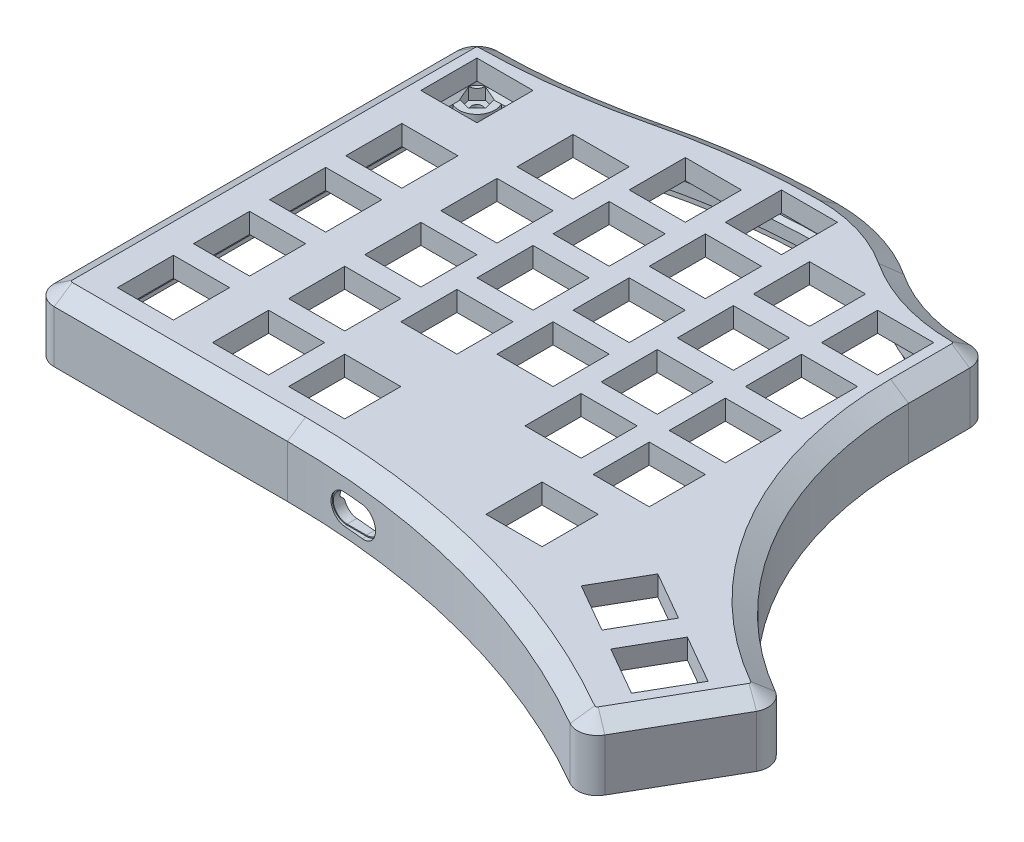
SolidWorks part; units mm, degrees
ref_plane "Front Plane" through (0, 0, 0) normal (0, 0, 1) x (1, 0, 0)
ref_plane "Top Plane" through (0, 0, 0) normal (0, 1, 0) x (1, 0, 0)
ref_plane "Right Plane" through (0, 0, 0) normal (1, 0, 0) x (0, 0, -1)
sketch "Main" plane through (0, 0, 0) normal (0, 1, 0) x (1, 0, 0)
  line L0 (6.4754, 3.5) -> (12.8, 6.5) construction
  line L1 (0, 0) -> (18, 0) construction
  line L2 (0, 0) -> (0, 18) construction
  line L3 (0, 18) -> (18, 18) construction
  line L4 (18, 0) -> (18, 18) construction
  line L5 (2, 16) -> (16, 16)
  line L6 (2, 16) -> (2, 2)
  line L7 (2, 2) -> (16, 2)
  line L8 (16, 16) -> (16, 2)
  line L18 (9, 9) -> (6.4754, 3.5) construction
  line L20 (9, 9) -> (12.8, 6.5) construction
  line L22 (25.4754, 12.5) -> (31.8, 15.5) construction
  line L23 (19, 9) -> (37, 9) construction
  line L24 (19, 9) -> (19, 27) construction
  line L25 (19, 27) -> (37, 27) construction
  line L26 (37, 9) -> (37, 27) construction
  line L27 (21, 25) -> (35, 25)
  line L28 (21, 25) -> (21, 11)
  line L29 (21, 11) -> (35, 11)
  line L30 (35, 25) -> (35, 11)
  line L31 (28, 18) -> (25.4754, 12.5) construction
  line L32 (28, 18) -> (31.8, 15.5) construction
  line L33 (44.4754, 17.5) -> (50.8, 20.5) construction
  line L34 (38, 14) -> (56, 14) construction
  line L35 (38, 14) -> (38, 32) construction
  line L36 (38, 32) -> (56, 32) construction
  line L37 (56, 14) -> (56, 32) construction
  line L38 (40, 30) -> (54, 30)
  line L39 (40, 30) -> (40, 16)
  line L40 (40, 16) -> (54, 16)
  line L41 (54, 30) -> (54, 16)
  line L42 (47, 23) -> (44.4754, 17.5) construction
  line L43 (47, 23) -> (50.8, 20.5) construction
  line L44 (63.4754, 5.5) -> (69.8, 8.5) construction
  line L45 (57, 2) -> (75, 2) construction
  line L46 (57, 2) -> (57, 20) construction
  line L47 (57, 20) -> (75, 20) construction
  line L48 (75, 2) -> (75, 20) construction
  line L49 (59, 18) -> (73, 18)
  line L50 (59, 18) -> (59, 4)
  line L51 (59, 4) -> (73, 4)
  line L52 (73, 18) -> (73, 4)
  line L53 (66, 11) -> (63.4754, 5.5) construction
  line L54 (66, 11) -> (69.8, 8.5) construction
  line L55 (82.4754, 3.5) -> (88.8, 6.5) construction
  line L56 (76, 0) -> (94, 0) construction
  line L57 (76, 0) -> (76, 18) construction
  line L58 (76, 18) -> (94, 18) construction
  line L59 (94, 0) -> (94, 18) construction
  line L60 (78, 16) -> (92, 16)
  line L61 (78, 16) -> (78, 2)
  line L62 (78, 2) -> (92, 2)
  line L63 (92, 16) -> (92, 2)
  line L64 (85, 9) -> (82.4754, 3.5) construction
  line L65 (85, 9) -> (88.8, 6.5) construction
  line L88 (2, -3) -> (16, -3)
  line L89 (2, -3) -> (2, -17)
  line L90 (2, -17) -> (16, -17)
  line L91 (16, -3) -> (16, -17)
  line L92 (21, 6) -> (35, 6)
  line L93 (21, 6) -> (21, -8)
  line L94 (21, -8) -> (35, -8)
  line L95 (35, 6) -> (35, -8)
  line L96 (40, 11) -> (54, 11)
  line L97 (40, 11) -> (40, -3)
  line L98 (40, -3) -> (54, -3)
  line L99 (54, 11) -> (54, -3)
  line L100 (59, -1) -> (73, -1)
  line L101 (59, -1) -> (59, -15)
  line L102 (59, -15) -> (73, -15)
  line L103 (73, -1) -> (73, -15)
  line L104 (78, -3) -> (92, -3)
  line L105 (78, -3) -> (78, -17)
  line L106 (78, -17) -> (92, -17)
  line L107 (92, -3) -> (92, -17)
  line L116 (6.4754, -15.5) -> (12.8, -12.5) construction
  line L117 (0, -19) -> (18, -19) construction
  line L118 (0, -19) -> (0, -1) construction
  line L119 (0, -1) -> (18, -1) construction
  line L120 (18, -19) -> (18, -1) construction
  line L121 (9, -10) -> (6.4754, -15.5) construction
  line L122 (9, -10) -> (12.8, -12.5) construction
  line L123 (25.4754, -6.5) -> (31.8, -3.5) construction
  line L124 (19, -10) -> (37, -10) construction
  line L125 (19, -10) -> (19, 8) construction
  line L126 (19, 8) -> (37, 8) construction
  line L127 (37, -10) -> (37, 8) construction
  line L128 (28, -1) -> (25.4754, -6.5) construction
  line L129 (28, -1) -> (31.8, -3.5) construction
  line L130 (44.4754, -1.5) -> (50.8, 1.5) construction
  line L131 (38, -5) -> (56, -5) construction
  line L132 (38, -5) -> (38, 13) construction
  line L133 (38, 13) -> (56, 13) construction
  line L134 (56, -5) -> (56, 13) construction
  line L135 (47, 4) -> (44.4754, -1.5) construction
  line L136 (47, 4) -> (50.8, 1.5) construction
  line L137 (63.4754, -13.5) -> (69.8, -10.5) construction
  line L138 (57, -17) -> (75, -17) construction
  line L139 (57, -17) -> (57, 1) construction
  line L140 (57, 1) -> (75, 1) construction
  line L141 (75, -17) -> (75, 1) construction
  line L142 (66, -8) -> (63.4754, -13.5) construction
  line L143 (66, -8) -> (69.8, -10.5) construction
  line L144 (82.4754, -15.5) -> (88.8, -12.5) construction
  line L145 (76, -19) -> (94, -19) construction
  line L146 (76, -19) -> (76, -1) construction
  line L147 (76, -1) -> (94, -1) construction
  line L148 (94, -19) -> (94, -1) construction
  line L149 (85, -10) -> (82.4754, -15.5) construction
  line L150 (85, -10) -> (88.8, -12.5) construction
  line L165 (2, -22) -> (16, -22)
  line L166 (2, -22) -> (2, -36)
  line L167 (2, -36) -> (16, -36)
  line L168 (16, -22) -> (16, -36)
  line L169 (21, -13) -> (35, -13)
  line L170 (21, -13) -> (21, -27)
  line L171 (21, -27) -> (35, -27)
  line L172 (35, -13) -> (35, -27)
  line L173 (40, -8) -> (54, -8)
  line L174 (40, -8) -> (40, -22)
  line L175 (40, -22) -> (54, -22)
  line L176 (54, -8) -> (54, -22)
  line L177 (59, -20) -> (73, -20)
  line L178 (59, -20) -> (59, -34)
  line L179 (59, -34) -> (73, -34)
  line L180 (73, -20) -> (73, -34)
  line L181 (78, -22) -> (92, -22)
  line L182 (78, -22) -> (78, -36)
  line L183 (78, -36) -> (92, -36)
  line L184 (92, -22) -> (92, -36)
  line L193 (6.4754, -34.5) -> (12.8, -31.5) construction
  line L194 (0, -38) -> (18, -38) construction
  line L195 (0, -38) -> (0, -20) construction
  line L196 (0, -20) -> (18, -20) construction
  line L197 (18, -38) -> (18, -20) construction
  line L198 (9, -29) -> (6.4754, -34.5) construction
  line L199 (9, -29) -> (12.8, -31.5) construction
  line L200 (25.4754, -25.5) -> (31.8, -22.5) construction
  line L201 (19, -29) -> (37, -29) construction
  line L202 (19, -29) -> (19, -11) construction
  line L203 (19, -11) -> (37, -11) construction
  line L204 (37, -29) -> (37, -11) construction
  line L205 (28, -20) -> (25.4754, -25.5) construction
  line L206 (28, -20) -> (31.8, -22.5) construction
  line L207 (44.4754, -20.5) -> (50.8, -17.5) construction
  line L208 (38, -24) -> (56, -24) construction
  line L209 (38, -24) -> (38, -6) construction
  line L210 (38, -6) -> (56, -6) construction
  line L211 (56, -24) -> (56, -6) construction
  line L212 (47, -15) -> (44.4754, -20.5) construction
  line L213 (47, -15) -> (50.8, -17.5) construction
  line L214 (63.4754, -32.5) -> (69.8, -29.5) construction
  line L215 (57, -36) -> (75, -36) construction
  line L216 (57, -36) -> (57, -18) construction
  line L217 (57, -18) -> (75, -18) construction
  line L218 (75, -36) -> (75, -18) construction
  line L219 (66, -27) -> (63.4754, -32.5) construction
  line L220 (66, -27) -> (69.8, -29.5) construction
  line L221 (82.4754, -34.5) -> (88.8, -31.5) construction
  line L222 (76, -38) -> (94, -38) construction
  line L223 (76, -38) -> (76, -20) construction
  line L224 (76, -20) -> (94, -20) construction
  line L225 (94, -38) -> (94, -20) construction
  line L226 (85, -29) -> (82.4754, -34.5) construction
  line L227 (85, -29) -> (88.8, -31.5) construction
  line L242 (2, -41) -> (16, -41)
  line L243 (2, -41) -> (2, -55)
  line L244 (2, -55) -> (16, -55)
  line L245 (16, -41) -> (16, -55)
  line L246 (21, -32) -> (35, -32)
  line L247 (21, -32) -> (21, -46)
  line L248 (21, -46) -> (35, -46)
  line L249 (35, -32) -> (35, -46)
  line L250 (40, -27) -> (54, -27)
  line L251 (40, -27) -> (40, -41)
  line L252 (40, -41) -> (54, -41)
  line L253 (54, -27) -> (54, -41)
  line L254 (59, -39) -> (73, -39)
  line L255 (59, -39) -> (59, -53)
  line L256 (59, -53) -> (73, -53)
  line L257 (73, -39) -> (73, -53)
  line L258 (78, -41) -> (92, -41)
  line L259 (78, -41) -> (78, -55)
  line L260 (78, -55) -> (92, -55)
  line L261 (92, -41) -> (92, -55)
  line L270 (6.4754, -53.5) -> (12.8, -50.5) construction
  line L271 (0, -57) -> (18, -57) construction
  line L272 (0, -57) -> (0, -39) construction
  line L273 (0, -39) -> (18, -39) construction
  line L274 (18, -57) -> (18, -39) construction
  line L275 (9, -48) -> (6.4754, -53.5) construction
  line L276 (9, -48) -> (12.8, -50.5) construction
  line L277 (25.4754, -44.5) -> (31.8, -41.5) construction
  line L278 (19, -48) -> (37, -48) construction
  line L279 (19, -48) -> (19, -30) construction
  line L280 (19, -30) -> (37, -30) construction
  line L281 (37, -48) -> (37, -30) construction
  line L282 (28, -39) -> (25.4754, -44.5) construction
  line L283 (28, -39) -> (31.8, -41.5) construction
  line L284 (44.4754, -39.5) -> (50.8, -36.5) construction
  line L285 (38, -43) -> (56, -43) construction
  line L286 (38, -43) -> (38, -25) construction
  line L287 (38, -25) -> (56, -25) construction
  line L288 (56, -43) -> (56, -25) construction
  line L289 (47, -34) -> (44.4754, -39.5) construction
  line L290 (47, -34) -> (50.8, -36.5) construction
  line L291 (63.4754, -51.5) -> (69.8, -48.5) construction
  line L292 (57, -55) -> (75, -55) construction
  line L293 (57, -55) -> (57, -37) construction
  line L294 (57, -37) -> (75, -37) construction
  line L295 (75, -55) -> (75, -37) construction
  line L296 (66, -46) -> (63.4754, -51.5) construction
  line L297 (66, -46) -> (69.8, -48.5) construction
  line L298 (82.4754, -53.5) -> (88.8, -50.5) construction
  line L299 (76, -57) -> (94, -57) construction
  line L300 (76, -57) -> (76, -39) construction
  line L301 (76, -39) -> (94, -39) construction
  line L302 (94, -57) -> (94, -39) construction
  line L303 (85, -48) -> (82.4754, -53.5) construction
  line L304 (85, -48) -> (88.8, -50.5) construction
  line L312 (6.4754, -72.5) -> (12.8, -69.5) construction
  line L313 (0, -76) -> (18, -76) construction
  line L314 (0, -76) -> (0, -58) construction
  line L315 (0, -58) -> (18, -58) construction
  line L316 (18, -76) -> (18, -58) construction
  line L317 (2, -60) -> (16, -60)
  line L318 (2, -60) -> (2, -74)
  line L323 (21, -60) -> (35, -60)
  line L324 (21, -60) -> (21, -74)
  line L325 (21, -74) -> (35, -74)
  line L326 (35, -60) -> (35, -74)
  line L327 (25.4754, -72.5) -> (31.8, -69.5) construction
  line L328 (19, -76) -> (37, -76) construction
  line L329 (19, -76) -> (19, -58) construction
  line L330 (-22.0246, 8) -> (-15.7, 11) construction
  line L331 (-28.5, 4.5) -> (-10.5, 4.5) construction
  line L332 (-28.5, 4.5) -> (-28.5, 22.5) construction
  line L333 (-28.5, 22.5) -> (-10.5, 22.5) construction
  line L334 (-10.5, 4.5) -> (-10.5, 22.5) construction
  line L335 (-26.5, 20.5) -> (-12.5, 20.5)
  line L336 (-26.5, 20.5) -> (-26.5, 6.5)
  line L337 (-26.5, 6.5) -> (-12.5, 6.5)
  line L338 (-12.5, 20.5) -> (-12.5, 6.5)
  line L339 (-19.5, 13.5) -> (-22.0246, 8) construction
  line L340 (-19.5, 13.5) -> (-15.7, 11) construction
  line L341 (-21.75, -41) -> (-7.75, -41)
  line L342 (-21.75, -41) -> (-21.75, -55)
  line L343 (-21.75, -55) -> (-7.75, -55)
  line L344 (-7.75, -41) -> (-7.75, -55)
  line L345 (-17.2746, -53.5) -> (-10.95, -50.5) construction
  line L346 (-28.5, -57) -> (-1, -57) construction
  line L347 (-28.5, -57) -> (-28.5, -39) construction
  line L348 (-28.5, -39) -> (-1, -39) construction
  line L349 (-1, -57) -> (-1, -39) construction
  line L350 (-14.75, -48) -> (-17.2746, -53.5) construction
  line L351 (-14.75, -48) -> (-10.95, -50.5) construction
  line L352 (-21.75, -22) -> (-7.75, -22)
  line L353 (-21.75, -22) -> (-21.75, -36)
  line L354 (2, -74) -> (16, -74)
  line L355 (16, -60) -> (16, -74)
  line L356 (9, -67) -> (6.4754, -72.5) construction
  line L357 (9, -67) -> (12.8, -69.5) construction
  line L358 (-17.2746, -72.5) -> (-10.95, -69.5) construction
  line L359 (-28.5, -76) -> (-1, -76) construction
  line L360 (-28.5, -76) -> (-28.5, -58) construction
  line L361 (-28.5, -58) -> (-1, -58) construction
  line L362 (-1, -76) -> (-1, -58) construction
  line L363 (-21.75, -60) -> (-7.75, -60)
  line L364 (-21.75, -60) -> (-21.75, -74)
  line L365 (-21.75, -74) -> (-7.75, -74)
  line L366 (-7.75, -60) -> (-7.75, -74)
  line L367 (-14.75, -67) -> (-17.2746, -72.5) construction
  line L368 (-14.75, -67) -> (-10.95, -69.5) construction
  line L369 (-21.75, -36) -> (-7.75, -36)
  line L370 (-7.75, -22) -> (-7.75, -36)
  line L371 (-17.2746, -34.5) -> (-10.95, -31.5) construction
  line L372 (-28.5, -38) -> (-1, -38) construction
  line L373 (-28.5, -38) -> (-28.5, -20) construction
  line L374 (-28.5, -20) -> (-1, -20) construction
  line L375 (-1, -38) -> (-1, -20) construction
  line L376 (-14.75, -29) -> (-17.2746, -34.5) construction
  line L377 (-14.75, -29) -> (-10.95, -31.5) construction
  line L378 (-21.75, -3) -> (-7.75, -3)
  line L379 (-21.75, -3) -> (-21.75, -17)
  line L380 (-21.75, -17) -> (-7.75, -17)
  line L381 (-7.75, -3) -> (-7.75, -17)
  line L382 (-17.2746, -15.5) -> (-10.95, -12.5) construction
  line L383 (-28.5, -19) -> (-1, -19) construction
  line L384 (-28.5, -19) -> (-28.5, -1) construction
  line L385 (-28.5, -1) -> (-1, -1) construction
  line L386 (-1, -19) -> (-1, -1) construction
  line L387 (-14.75, -10) -> (-17.2746, -15.5) construction
  line L388 (-14.75, -10) -> (-10.95, -12.5) construction
  line L393 (109.2068, -61.578) -> (124.8116, -70.5498) construction
  line L394 (109.2068, -61.578) -> (95.5, -85.4186) construction
  line L398 (124.8116, -70.5498) -> (111.1047, -94.3903) construction
  line L402 (77.7254, -75.5) -> (84.05, -72.5) construction
  line L403 (66.5, -79) -> (94, -79) construction
  line L404 (66.5, -79) -> (66.5, -61) construction
  line L405 (66.5, -61) -> (94, -61) construction
  line L406 (94, -79) -> (94, -61) construction
  line L407 (73.25, -63) -> (87.25, -63)
  line L408 (73.25, -63) -> (73.25, -77)
  line L409 (73.25, -77) -> (87.25, -77)
  line L410 (87.25, -63) -> (87.25, -77)
  line L411 (80.25, -70) -> (77.7254, -75.5) construction
  line L412 (80.25, -70) -> (84.05, -72.5) construction
  line L413 (95.5, -85.4186) -> (111.1047, -94.3903) construction
  line L414 (95.5, -85.4186) -> (124.8116, -70.5498) construction
  line L415 (80.25, -130) -> (110.1558, -77.9842) construction
  line L416 (107.5763, -68.4267) -> (119.7133, -75.4047)
  line L417 (107.5763, -68.4267) -> (100.5983, -80.5637)
  line L418 (119.7133, -75.4047) -> (112.7353, -87.5417)
  line L419 (100.5983, -80.5637) -> (112.7353, -87.5417)
  line L420 (107.5763, -68.4267) -> (112.7353, -87.5417) construction
  line L421 (105.2258, -81.494) -> (110.1558, -77.9842) construction
  line L422 (110.1558, -77.9842) -> (112.204, -82.0455) construction
  line L423 (112.204, -82.0455) -> (105.2258, -81.494) construction
  line L424 (126.5454, -71.5466) -> (142.1502, -80.5184) construction
  line L425 (126.5454, -71.5466) -> (112.8386, -95.3872) construction
  line L426 (142.1502, -80.5184) -> (128.4433, -104.3589) construction
  line L427 (112.8386, -95.3872) -> (128.4433, -104.3589) construction
  line L428 (112.8386, -95.3872) -> (142.1502, -80.5184) construction
  line L430 (124.9149, -78.3953) -> (137.0519, -85.3733)
  line L431 (124.9149, -78.3953) -> (117.9369, -90.5323)
  line L432 (137.0519, -85.3733) -> (130.0739, -97.5103)
  line L433 (117.9369, -90.5323) -> (130.0739, -97.5103)
  line L434 (124.9149, -78.3953) -> (130.0739, -97.5103) construction
  line L435 (122.5644, -91.4626) -> (127.4944, -87.9528) construction
  line L436 (127.4944, -87.9528) -> (129.5426, -92.0141) construction
  line L437 (129.5426, -92.0141) -> (122.5644, -91.4626) construction
  line L448 (19, -58) -> (37, -58) construction
  line L449 (37, -76) -> (37, -58) construction
  line L450 (28, -67) -> (25.4754, -72.5) construction
  line L451 (28, -67) -> (31.8, -69.5) construction
  circle A0 centre (9, 9) radius 2 construction
  circle A1 centre (6.4754, 3.5) radius 1.5 construction
  circle A2 centre (12.8, 6.5) radius 1.5 construction
  circle A6 centre (28, 18) radius 2 construction
  circle A7 centre (25.4754, 12.5) radius 1.5 construction
  circle A8 centre (31.8, 15.5) radius 1.5 construction
  circle A9 centre (47, 23) radius 2 construction
  circle A10 centre (44.4754, 17.5) radius 1.5 construction
  circle A11 centre (50.8, 20.5) radius 1.5 construction
  circle A12 centre (66, 11) radius 2 construction
  circle A13 centre (63.4754, 5.5) radius 1.5 construction
  circle A14 centre (69.8, 8.5) radius 1.5 construction
  circle A15 centre (85, 9) radius 2 construction
  circle A16 centre (82.4754, 3.5) radius 1.5 construction
  circle A17 centre (88.8, 6.5) radius 1.5 construction
  circle A24 centre (9, -10) radius 2 construction
  circle A25 centre (6.4754, -15.5) radius 1.5 construction
  circle A26 centre (12.8, -12.5) radius 1.5 construction
  circle A27 centre (28, -1) radius 2 construction
  circle A28 centre (25.4754, -6.5) radius 1.5 construction
  circle A29 centre (31.8, -3.5) radius 1.5 construction
  circle A30 centre (47, 4) radius 2 construction
  circle A31 centre (44.4754, -1.5) radius 1.5 construction
  circle A32 centre (50.8, 1.5) radius 1.5 construction
  circle A33 centre (66, -8) radius 2 construction
  circle A34 centre (63.4754, -13.5) radius 1.5 construction
  circle A35 centre (69.8, -10.5) radius 1.5 construction
  circle A36 centre (85, -10) radius 2 construction
  circle A37 centre (82.4754, -15.5) radius 1.5 construction
  circle A38 centre (88.8, -12.5) radius 1.5 construction
  circle A45 centre (9, -29) radius 2 construction
  circle A46 centre (6.4754, -34.5) radius 1.5 construction
  circle A47 centre (12.8, -31.5) radius 1.5 construction
  circle A48 centre (28, -20) radius 2 construction
  circle A49 centre (25.4754, -25.5) radius 1.5 construction
  circle A50 centre (31.8, -22.5) radius 1.5 construction
  circle A51 centre (47, -15) radius 2 construction
  circle A52 centre (44.4754, -20.5) radius 1.5 construction
  circle A53 centre (50.8, -17.5) radius 1.5 construction
  circle A54 centre (66, -27) radius 2 construction
  circle A55 centre (63.4754, -32.5) radius 1.5 construction
  circle A56 centre (69.8, -29.5) radius 1.5 construction
  circle A57 centre (85, -29) radius 2 construction
  circle A58 centre (82.4754, -34.5) radius 1.5 construction
  circle A59 centre (88.8, -31.5) radius 1.5 construction
  circle A63 centre (9, -67) radius 2 construction
  circle A64 centre (6.4754, -72.5) radius 1.5 construction
  circle A65 centre (12.8, -69.5) radius 1.5 construction
  circle A66 centre (9, -48) radius 2 construction
  circle A67 centre (6.4754, -53.5) radius 1.5 construction
  circle A68 centre (12.8, -50.5) radius 1.5 construction
  circle A69 centre (28, -39) radius 2 construction
  circle A70 centre (25.4754, -44.5) radius 1.5 construction
  circle A71 centre (31.8, -41.5) radius 1.5 construction
  circle A72 centre (47, -34) radius 2 construction
  circle A73 centre (44.4754, -39.5) radius 1.5 construction
  circle A74 centre (50.8, -36.5) radius 1.5 construction
  circle A75 centre (66, -46) radius 2 construction
  circle A76 centre (63.4754, -51.5) radius 1.5 construction
  circle A77 centre (69.8, -48.5) radius 1.5 construction
  circle A78 centre (85, -48) radius 2 construction
  circle A79 centre (82.4754, -53.5) radius 1.5 construction
  circle A80 centre (88.8, -50.5) radius 1.5 construction
  circle A81 centre (-14.75, -67) radius 2 construction
  circle A82 centre (-17.2746, -72.5) radius 1.5 construction
  circle A83 centre (-10.95, -69.5) radius 1.5 construction
  circle A84 centre (28, -67) radius 2 construction
  circle A85 centre (25.4754, -72.5) radius 1.5 construction
  circle A86 centre (31.8, -69.5) radius 1.5 construction
  circle A87 centre (-19.5, 13.5) radius 2 construction
  circle A88 centre (-22.0246, 8) radius 1.5 construction
  circle A89 centre (-15.7, 11) radius 1.5 construction
  circle A90 centre (-14.75, -48) radius 2 construction
  circle A91 centre (-17.2746, -53.5) radius 1.5 construction
  circle A92 centre (-10.95, -50.5) radius 1.5 construction
  circle A93 centre (-14.75, -29) radius 2 construction
  circle A94 centre (-17.2746, -34.5) radius 1.5 construction
  circle A95 centre (-10.95, -31.5) radius 1.5 construction
  circle A96 centre (-14.75, -10) radius 2 construction
  circle A97 centre (-17.2746, -15.5) radius 1.5 construction
  circle A98 centre (-10.95, -12.5) radius 1.5 construction
  circle A102 centre (80.25, -70) radius 2 construction
  circle A103 centre (77.7254, -75.5) radius 1.5 construction
  circle A104 centre (84.05, -72.5) radius 1.5 construction
  circle A105 centre (80.25, -130) radius 60 construction
  circle A106 centre (110.1558, -77.9842) radius 2 construction
  circle A107 centre (105.2258, -81.494) radius 1.5 construction
  circle A108 centre (112.204, -82.0455) radius 1.5 construction
  circle A109 centre (127.4944, -87.9528) radius 2 construction
  circle A110 centre (122.5644, -91.4626) radius 1.5 construction
  circle A111 centre (129.5426, -92.0141) radius 1.5 construction
  circle A112 centre (62, -66) radius 1.5 construction
  point P9 (9, 16)
  point P10 (9, 18)
  point P11 (2, 9)
  point P12 (0, 9)
  point P30 (28, 25)
  point P31 (28, 27)
  point P32 (21, 18)
  point P33 (19, 18)
  point P46 (47, 30)
  point P47 (47, 32)
  point P48 (40, 23)
  point P49 (38, 23)
  point P64 (66, 18)
  point P65 (66, 20)
  point P66 (59, 11)
  point P67 (57, 11)
  point P82 (85, 16)
  point P83 (85, 18)
  point P84 (78, 9)
  point P85 (76, 9)
  point P102 (9, -60)
  point P103 (9, -58)
  point P104 (2, -67)
  point P105 (0, -67)
  point P124 (-14.75, -60)
  point P125 (-14.75, -58)
  point P126 (-21.75, -67)
  point P127 (-28.5, -67)
  point P297 (-19.5, 20.5)
  point P298 (-19.5, 22.5)
  point P299 (-26.5, 13.5)
  point P300 (-28.5, 13.5)
  point P423 (103.3024, -89.9045)
  point P444 (80.25, -63)
  point P445 (80.25, -61)
  point P446 (73.25, -70)
  point P447 (66.5, -70)
  dimension "D6" = 4
  dimension "D7" = 3
  dimension "D10" = 1
  dimension "D11" = 12
  dimension "D21" = 9.5
  dimension "D22" = 1.5
  dimension "D26" = 120
  dimension "D28" = 3
  dimension "D1" = 18
  dimension "D2" = 14
  dimension "D3" = 3.2
  dimension "D4" = 4.5
  dimension "D5" = 7
  dimension "D8" = 1
  dimension "D9" = 5
  dimension "D12" = 1
  dimension "D13" = 9
  dimension "D14" = 1
  dimension "D15" = 2
  dimension "D16" = 2
  dimension "D17" = 27.5
  dimension "D18" = 1
  dimension "D20" = 1
  dimension "D24" = 1
  dimension "D25" = 8
  dimension "D27" = 2
  dimension "D29" = 15
  dimension "D30" = 32
  dimension "D19" = 4
  dimension "D23" = 4
sketch "Sketch1" plane through (0, 0, 0) normal (0, 1, 0) x (1, 0, 0)
  line L0 (-33.5, 22.5) -> (-33.5, -78)
  line L1 (-28.5, -83) -> (29.7127, -83)
  line L2 (132.778, -106.8511) -> (146.594, -82.8206)
  line L3 (99, 2.7142) -> (99, 18)
  line L6 (-28.5, -76) -> (-1, -76) construction
  line L7 (-28.5, -76) -> (-28.5, -58) construction
  line L8 (144.6447, -76.1796) -> (94, -47.0621) construction
  line L9 (142.1502, -80.5184) -> (128.4433, -104.3589) construction
  line L10 (94, 0) -> (94, 18) construction
  line L11 (94, -57) -> (94, -39) construction
  line L12 (128.4433, -104.3589) -> (125.9512, -108.6936) construction
  line L13 (109.2068, -61.578) -> (124.8116, -70.5498) construction
  line L14 (125.9512, -108.6936) -> (74.3045, -79) construction
  line L15 (66.5, -79) -> (94, -79) construction
  line L16 (38, 32) -> (56, 32) construction
  line L17 (95.5, -85.4186) -> (111.1047, -94.3903) construction
  line L18 (47, 37) -> (47, 32) construction
  line L19 (47, 37) -> (-33.5, 37) construction
  line L20 (94, 23) -> (56, 23) construction
  line L21 (56, 14) -> (56, 32) construction
  line L22 (-31.5, 22.5) -> (-31.5, -78) construction
  line L24 (-28.5, -81) -> (29.7127, -81) construction
  line L25 (131.0441, -105.8542) -> (144.8356, -81.8665) construction
  line L26 (97, 2.7142) -> (97, 18) construction
  line L39 (107.5763, -68.4267) -> (119.7133, -75.4047)
  line L40 (-26.5, 20.5) -> (-12.5, 20.5)
  line L41 (-26.5, 20.5) -> (-26.5, 6.5)
  line L42 (-26.5, 6.5) -> (-12.5, 6.5)
  line L43 (-12.5, 20.5) -> (-12.5, 6.5)
  line L44 (-21.75, -3) -> (-7.75, -3)
  line L45 (-21.75, -3) -> (-21.75, -17)
  line L46 (-21.75, -17) -> (-7.75, -17)
  line L47 (-7.75, -3) -> (-7.75, -17)
  line L48 (-21.75, -22) -> (-7.75, -22)
  line L49 (-21.75, -22) -> (-21.75, -36)
  line L50 (-21.75, -36) -> (-7.75, -36)
  line L51 (-7.75, -22) -> (-7.75, -36)
  line L52 (-21.75, -41) -> (-7.75, -41)
  line L53 (-21.75, -41) -> (-21.75, -55)
  line L54 (-21.75, -55) -> (-7.75, -55)
  line L55 (-7.75, -41) -> (-7.75, -55)
  line L56 (-21.75, -60) -> (-7.75, -60)
  line L57 (-21.75, -60) -> (-21.75, -74)
  line L58 (-21.75, -74) -> (-7.75, -74)
  line L59 (-7.75, -60) -> (-7.75, -74)
  line L60 (2, 16) -> (16, 16)
  line L61 (2, 16) -> (2, 2)
  line L62 (2, 2) -> (16, 2)
  line L63 (16, 16) -> (16, 2)
  line L64 (2, -3) -> (16, -3)
  line L65 (2, -3) -> (2, -17)
  line L66 (2, -17) -> (16, -17)
  line L67 (16, -3) -> (16, -17)
  line L68 (2, -22) -> (16, -22)
  line L69 (2, -22) -> (2, -36)
  line L70 (2, -36) -> (16, -36)
  line L71 (16, -22) -> (16, -36)
  line L72 (2, -41) -> (16, -41)
  line L73 (2, -41) -> (2, -55)
  line L74 (2, -55) -> (16, -55)
  line L75 (16, -41) -> (16, -55)
  line L76 (2, -60) -> (16, -60)
  line L77 (2, -60) -> (2, -74)
  line L78 (2, -74) -> (16, -74)
  line L79 (16, -60) -> (16, -74)
  line L80 (21, -60) -> (35, -60)
  line L81 (21, -60) -> (21, -74)
  line L82 (21, -74) -> (35, -74)
  line L83 (35, -60) -> (35, -74)
  line L84 (21, -32) -> (35, -32)
  line L85 (21, -32) -> (21, -46)
  line L86 (21, -46) -> (35, -46)
  line L87 (35, -32) -> (35, -46)
  line L88 (21, 25) -> (35, 25)
  line L89 (21, 25) -> (21, 11)
  line L90 (21, 11) -> (35, 11)
  line L91 (35, 25) -> (35, 11)
  line L92 (21, 6) -> (35, 6)
  line L93 (21, 6) -> (21, -8)
  line L94 (21, -8) -> (35, -8)
  line L95 (35, 6) -> (35, -8)
  line L96 (21, -13) -> (35, -13)
  line L97 (21, -13) -> (21, -27)
  line L98 (21, -27) -> (35, -27)
  line L99 (35, -13) -> (35, -27)
  line L100 (40, 30) -> (54, 30)
  line L101 (40, 30) -> (40, 16)
  line L102 (40, 16) -> (54, 16)
  line L103 (54, 30) -> (54, 16)
  line L104 (40, 11) -> (54, 11)
  line L105 (40, 11) -> (40, -3)
  line L106 (40, -3) -> (54, -3)
  line L107 (54, 11) -> (54, -3)
  line L108 (40, -8) -> (54, -8)
  line L109 (40, -8) -> (40, -22)
  line L110 (40, -22) -> (54, -22)
  line L111 (54, -8) -> (54, -22)
  line L112 (40, -27) -> (54, -27)
  line L113 (40, -27) -> (40, -41)
  line L114 (40, -41) -> (54, -41)
  line L115 (54, -27) -> (54, -41)
  line L116 (59, 18) -> (73, 18)
  line L117 (59, 18) -> (59, 4)
  line L118 (59, 4) -> (73, 4)
  line L119 (73, 18) -> (73, 4)
  line L120 (78, 16) -> (92, 16)
  line L121 (78, 16) -> (78, 2)
  line L122 (78, 2) -> (92, 2)
  line L123 (92, 16) -> (92, 2)
  line L124 (59, -1) -> (73, -1)
  line L125 (59, -1) -> (59, -15)
  line L126 (59, -15) -> (73, -15)
  line L127 (73, -1) -> (73, -15)
  line L128 (78, -3) -> (92, -3)
  line L129 (78, -3) -> (78, -17)
  line L130 (78, -17) -> (92, -17)
  line L131 (92, -3) -> (92, -17)
  line L132 (59, -20) -> (73, -20)
  line L133 (59, -20) -> (59, -34)
  line L134 (59, -34) -> (73, -34)
  line L135 (73, -20) -> (73, -34)
  line L136 (78, -22) -> (92, -22)
  line L137 (78, -22) -> (78, -36)
  line L138 (78, -36) -> (92, -36)
  line L139 (92, -22) -> (92, -36)
  line L140 (59, -39) -> (73, -39)
  line L141 (59, -39) -> (59, -53)
  line L142 (59, -53) -> (73, -53)
  line L143 (73, -39) -> (73, -53)
  line L144 (78, -41) -> (92, -41)
  line L145 (78, -41) -> (78, -55)
  line L146 (78, -55) -> (92, -55)
  line L147 (92, -41) -> (92, -55)
  line L148 (73.25, -63) -> (87.25, -63)
  line L149 (73.25, -63) -> (73.25, -77)
  line L150 (73.25, -77) -> (87.25, -77)
  line L151 (87.25, -63) -> (87.25, -77)
  line L152 (107.5763, -68.4267) -> (100.5983, -80.5637)
  line L153 (119.7133, -75.4047) -> (112.7353, -87.5417)
  line L154 (100.5983, -80.5637) -> (112.7353, -87.5417)
  line L155 (124.9149, -78.3953) -> (137.0519, -85.3733)
  line L156 (124.9149, -78.3953) -> (117.9369, -90.5323)
  line L157 (137.0519, -85.3733) -> (130.0739, -97.5103)
  line L158 (117.9369, -90.5323) -> (130.0739, -97.5103)
  arc A0 (29.7127, -83) -> (125.9512, -108.6936) centre (29.7127, -276.0835) cw
  arc A4 (94, 23) -> (70.5, 30) centre (94, 65.9464) cw
  arc A5 (70.5, 30) -> (47, 37) centre (47, -5.9464) ccw
  arc A6 (47, 37) -> (8.1496, 32.2427) centre (47, -124.0147) ccw
  arc A7 (8.1496, 32.2427) -> (-28.5663, 27.4996) centre (-30.7009, 188.5001) cw
  arc A10 (125.9512, -108.6936) -> (132.778, -106.8511) centre (128.4433, -104.3589) ccw
  arc A11 (-33.5, -78) -> (-28.5, -83) centre (-28.5, -78) ccw
  arc A14 (146.594, -82.8206) -> (144.6447, -76.1796) centre (142.1502, -80.5184) ccw
  arc A15 (144.6447, -76.1796) -> (99, 2.7142) centre (190.0036, 2.7142) cw
  arc A16 (99, 18) -> (94, 23) centre (94, 18) ccw
  arc A17 (-33.5, 22.5) -> (-28.5663, 27.4996) centre (-28.5, 22.5) cw
  arc A18 (8.6321, 30.3018) -> (-28.5398, 25.4997) centre (-30.7009, 188.5001) cw construction
  arc A19 (-31.5, 22.5) -> (-28.5398, 25.4997) centre (-28.5, 22.5) cw construction
  arc A20 (-31.5, -78) -> (-28.5, -81) centre (-28.5, -78) ccw construction
  arc A21 (29.7127, -81) -> (126.9481, -106.9597) centre (29.7127, -276.0835) cw construction
  arc A22 (126.9481, -106.9597) -> (131.0441, -105.8542) centre (128.4433, -104.3589) ccw construction
  arc A23 (144.8356, -81.8665) -> (143.6478, -77.9134) centre (142.1502, -80.5184) ccw construction
  arc A24 (143.6478, -77.9134) -> (97, 2.7142) centre (190.0036, 2.7142) cw construction
  arc A25 (97, 18) -> (94, 21) centre (94, 18) ccw construction
  arc A26 (94, 21) -> (69.4056, 28.326) centre (94, 65.9464) cw construction
  arc A27 (69.4056, 28.326) -> (47, 35) centre (47, -5.9464) ccw construction
  arc A28 (47, 35) -> (8.6321, 30.3018) centre (47, -124.0147) ccw construction
  dimension "D1" = 7
  dimension "D2" = 5
  dimension "D7" = 5.0048
  dimension "D8" = 5
  dimension "D3" = 5
  dimension "D4" = 5
  dimension "D5" = 5
  dimension "D6" = 5
  dimension "D9" = 2
extrude "Main_plate" add sketch "Sketch1" against normal blind 5
chamfer "Main_plate_chamfer" distance 3 distance2 4.5 15 edges at (146.9524, 0, 79.1088) (111.2334, 0, 42.859) (99, 0, -10.3571) (97.5355, 0, -21.5355) (81.7398, 0, -24.7872) (59.2602, 0, -35.2128) (27.4297, 0, -35.8063) (-10.0716, 0, -28.8124) (-32.0589, 0, -26.012) (139.686, 0, 94.8358) (-33.5, 0, 27.75) (129.7462, 0, 109.1862) (-32.0355, 0, 81.5355) (79.5173, 0, 89.534) (0.6063, 0, 83) first distance on face at (146.2859, -2.5, 79.3044) first distance on face at (116.5279, -2.5, 39.7958) first distance on face at (99, -2.5, -10.3571) first distance on face at (97.0178, -2.5, -21.0178) first distance on face at (81.9949, -2.5, -25.6436) first distance on face at (59.0051, -2.5, -34.3564) first distance on face at (27.5022, -2.5, -35.2138) first distance on face at (-10.14, -2.5, -29.3418) first distance on face at (-31.546, -2.5, -25.5059) first distance on face at (139.686, -2.5, 94.8358) first distance on face at (-33.5, -2.5, 27.75) first distance on face at (129.5554, -2.5, 108.4793) first distance on face at (-31.5178, -2.5, 81.0178) first distance on face at (78.6746, -2.5, 92.6904) first distance on face at (0.6063, -2.5, 83)
sketch "Sketch3" plane through (0, -5, 0) normal (0, -1, 0) x (1, 0, 0)
  line L0 (-28.5, 83) -> (29.7127, 83)
  line L1 (132.778, 106.8511) -> (146.594, 82.8206)
  line L2 (-33.5, 78) -> (-33.5, -22.5)
  line L3 (99, -18) -> (99, -2.7142)
  line L4 (-28.5, 81) -> (29.7127, 81)
  line L5 (131.0441, 105.8542) -> (144.8356, 81.8665)
  line L6 (97, -18) -> (97, -2.7142)
  line L7 (-31.5, 78) -> (-31.5, -22.5)
  arc A0 (29.7127, 83) -> (125.9512, 108.6936) centre (29.7127, 276.0835) ccw
  arc A1 (125.9512, 108.6936) -> (132.778, 106.8511) centre (128.4433, 104.3589) cw
  arc A2 (-28.5, 83) -> (-33.5, 78) centre (-28.5, 78) ccw
  arc A3 (-33.5, -22.5) -> (-28.5663, -27.4996) centre (-28.5, -22.5) ccw
  arc A4 (-28.5663, -27.4996) -> (8.1496, -32.2427) centre (-30.7009, -188.5001) cw
  arc A5 (8.1496, -32.2427) -> (47, -37) centre (47, 124.0147) ccw
  arc A6 (47, -37) -> (70.5, -30) centre (47, 5.9464) ccw
  arc A7 (70.5, -30) -> (94, -23) centre (94, -65.9464) cw
  arc A8 (94, -23) -> (99, -18) centre (94, -18) ccw
  arc A10 (144.6447, 76.1796) -> (146.594, 82.8206) centre (142.1502, 80.5184) ccw
  arc A11 (144.6447, 76.1796) -> (99, -2.7142) centre (190.0036, -2.7142) ccw
  arc A12 (29.7127, 81) -> (126.9481, 106.9597) centre (29.7127, 276.0835) ccw
  arc A13 (126.9481, 106.9597) -> (131.0441, 105.8542) centre (128.4433, 104.3589) cw
  arc A14 (143.6478, 77.9134) -> (144.8356, 81.8665) centre (142.1502, 80.5184) ccw
  arc A15 (143.6478, 77.9134) -> (97, -2.7142) centre (190.0036, -2.7142) ccw
  arc A16 (94, -21) -> (97, -18) centre (94, -18) ccw
  arc A17 (69.4056, -28.326) -> (94, -21) centre (94, -65.9464) cw
  arc A18 (47, -35) -> (69.4056, -28.326) centre (47, 5.9464) ccw
  arc A19 (8.6321, -30.3018) -> (47, -35) centre (47, 124.0147) ccw
  arc A20 (-28.5398, -25.4997) -> (8.6321, -30.3018) centre (-30.7009, -188.5001) cw
  arc A21 (-31.5, -22.5) -> (-28.5398, -25.4997) centre (-28.5, -22.5) ccw
  arc A22 (-28.5, 81) -> (-31.5, 78) centre (-28.5, 78) ccw
  dimension "D1" = 2
extrude "Wall" add sketch "Sketch3" along normal blind 11
sketch "Sketch4" plane through (0, -5, 0) normal (0, -1, 0) x (1, 0, 0)
  line L0 (47, 41) -> (47, 81.7675) construction
  line L1 (40, 41) -> (54, 41) construction
  line L2 (54.62, 79) -> (54.62, 46) construction
  line L3 (29.7127, 81) -> (-28.5, 81) construction
  line L4 (40.88, 46) -> (37.88, 46)
  line L5 (53.12, 79) -> (56.12, 79)
  line L6 (53.12, 79) -> (53.12, 46)
  line L7 (53.12, 46) -> (56.12, 46)
  line L8 (56.12, 79) -> (56.12, 46)
  line L9 (37.88, 79) -> (37.88, 46)
  line L10 (40.88, 79) -> (40.88, 46)
  line L11 (40.88, 79) -> (37.88, 79)
  arc A0 (29.7127, 81) -> (126.9481, 106.9597) centre (29.7127, 276.0835) ccw construction
  point P15 (54.62, 79)
  dimension "D1" = 7.62
  dimension "D2" = 2
  dimension "D3" = 33
  dimension "D4" = 3
extrude "For_pins_recess" cut sketch "Sketch4" against normal blind 2
ref_plane "Plane1" through (0, -14, 0) normal (0, -1, 0) x (-1, 0, 0)
sketch "Sketch8" plane through (0, -14, 0) normal (0, -1, 0) x (-1, 0, 0)
  line L41 (-143.9531, -81.395) -> (-130.1772, -105.3558)
  line L42 (-96, 18) -> (-96, 2.7142)
  line L43 (30.5, -78) -> (30.5, 22.5)
  line L44 (-29.7127, -80) -> (28.5, -80)
  line L45 (-143.9531, -81.395) -> (-130.1772, -105.3558)
  line L46 (-96, 18) -> (-96, 2.7142)
  line L47 (30.5, -78) -> (30.5, 22.5)
  line L48 (-29.7127, -80) -> (28.5, -80)
  line L86 (-144.8356, -81.8665) -> (-131.0441, -105.8542)
  line L87 (-97, 18) -> (-97, 2.7142)
  line L88 (31.5, -78) -> (31.5, 22.5)
  line L89 (-29.7127, -81) -> (28.5, -81)
  line L90 (-144.8356, -81.8665) -> (-131.0441, -105.8542)
  line L91 (-97, 18) -> (-97, 2.7142)
  line L92 (31.5, -78) -> (31.5, 22.5)
  line L93 (-29.7127, -81) -> (28.5, -81)
  arc A94 (-29.7127, -80) -> (-127.4465, -106.0928) centre (-29.7127, -276.0835) ccw
  arc A95 (-130.1772, -105.3558) -> (-127.4465, -106.0928) centre (-128.4433, -104.3589) ccw
  arc A96 (-143.1494, -78.7803) -> (-143.9531, -81.395) centre (-142.1502, -80.5184) ccw
  arc A97 (-143.1494, -78.7803) -> (-96, 2.7142) centre (-190.0036, 2.7142) ccw
  arc A98 (-94, 20) -> (-96, 18) centre (-94, 18) ccw
  arc A99 (-94, 20) -> (-68.8584, 27.489) centre (-94, 65.9464) ccw
  arc A100 (-47, 34) -> (-68.8584, 27.489) centre (-47, -5.9464) ccw
  arc A101 (-8.8734, 29.3313) -> (-47, 34) centre (-47, -124.0147) ccw
  arc A102 (-8.8734, 29.3313) -> (28.5265, 24.4998) centre (30.7009, 188.5001) ccw
  arc A103 (30.5, 22.5) -> (28.5265, 24.4998) centre (28.5, 22.5) ccw
  arc A104 (28.5, -80) -> (30.5, -78) centre (28.5, -78) ccw
  arc A105 (-29.7127, -80) -> (-127.4465, -106.0928) centre (-29.7127, -276.0835) ccw
  arc A106 (-130.1772, -105.3558) -> (-127.4465, -106.0928) centre (-128.4433, -104.3589) ccw
  arc A107 (-143.1494, -78.7803) -> (-143.9531, -81.395) centre (-142.1502, -80.5184) ccw
  arc A108 (-143.1494, -78.7803) -> (-96, 2.7142) centre (-190.0036, 2.7142) ccw
  arc A109 (-94, 20) -> (-96, 18) centre (-94, 18) ccw
  arc A110 (-94, 20) -> (-68.8584, 27.489) centre (-94, 65.9464) ccw
  arc A111 (-47, 34) -> (-68.8584, 27.489) centre (-47, -5.9464) ccw
  arc A112 (-8.8734, 29.3313) -> (-47, 34) centre (-47, -124.0147) ccw
  arc A113 (-8.8734, 29.3313) -> (28.5265, 24.4998) centre (30.7009, 188.5001) ccw
  arc A114 (30.5, 22.5) -> (28.5265, 24.4998) centre (28.5, 22.5) ccw
  arc A115 (28.5, -80) -> (30.5, -78) centre (28.5, -78) ccw
  arc A199 (-29.7127, -81) -> (-126.9481, -106.9597) centre (-29.7127, -276.0835) ccw
  arc A200 (-131.0441, -105.8542) -> (-126.9481, -106.9597) centre (-128.4433, -104.3589) ccw
  arc A201 (-143.6478, -77.9134) -> (-144.8356, -81.8665) centre (-142.1502, -80.5184) ccw
  arc A202 (-143.6478, -77.9134) -> (-97, 2.7142) centre (-190.0036, 2.7142) ccw
  arc A203 (-94, 21) -> (-97, 18) centre (-94, 18) ccw
  arc A204 (-94, 21) -> (-69.4056, 28.326) centre (-94, 65.9464) ccw
  arc A205 (-47, 35) -> (-69.4056, 28.326) centre (-47, -5.9464) ccw
  arc A206 (-8.6321, 30.3018) -> (-47, 35) centre (-47, -124.0147) ccw
  arc A207 (-8.6321, 30.3018) -> (28.5398, 25.4997) centre (30.7009, 188.5001) ccw
  arc A208 (31.5, 22.5) -> (28.5398, 25.4997) centre (28.5, 22.5) ccw
  arc A209 (28.5, -81) -> (31.5, -78) centre (28.5, -78) ccw
  arc A210 (-29.7127, -81) -> (-126.9481, -106.9597) centre (-29.7127, -276.0835) ccw
  arc A211 (-131.0441, -105.8542) -> (-126.9481, -106.9597) centre (-128.4433, -104.3589) ccw
  arc A212 (-143.6478, -77.9134) -> (-144.8356, -81.8665) centre (-142.1502, -80.5184) ccw
  arc A213 (-143.6478, -77.9134) -> (-97, 2.7142) centre (-190.0036, 2.7142) ccw
  arc A214 (-94, 21) -> (-97, 18) centre (-94, 18) ccw
  arc A215 (-94, 21) -> (-69.4056, 28.326) centre (-94, 65.9464) ccw
  arc A216 (-47, 35) -> (-69.4056, 28.326) centre (-47, -5.9464) ccw
  arc A217 (-8.6321, 30.3018) -> (-47, 35) centre (-47, -124.0147) ccw
  arc A218 (-8.6321, 30.3018) -> (28.5398, 25.4997) centre (30.7009, 188.5001) ccw
  arc A219 (31.5, 22.5) -> (28.5398, 25.4997) centre (28.5, 22.5) ccw
  arc A220 (28.5, -81) -> (31.5, -78) centre (28.5, -78) ccw
  dimension "D1" = 1
  dimension "D2" = 0
extrude "Side" add sketch "Sketch8" against normal blind 3
sketch "Sketch6" plane through (0, -14, 0) normal (0, -1, 0) x (1, 0, 0)
  line L14 (132.7159, 102.9465) -> (131.0441, 105.8542)
  line L41 (144.8356, 81.8665) -> (131.0441, 105.8542) construction
  line L43 (126.9481, 106.9597) -> (124.0483, 105.3253)
  line L44 (144.8356, 81.8665) -> (143.0792, 84.9214)
  line L45 (129.9433, 101.7609) -> (131.4433, 104.3589) construction
  line L46 (131.4433, 104.3589) -> (129.9433, 106.957) construction
  line L47 (129.9433, 106.957) -> (126.9433, 106.957) construction
  line L48 (126.9433, 106.957) -> (125.4433, 104.3589) construction
  line L49 (125.4433, 104.3589) -> (126.9433, 101.7609) construction
  line L50 (126.9433, 101.7609) -> (129.9433, 101.7609) construction
  line L51 (143.6478, 77.9134) -> (140.8192, 76.2197)
  line L52 (-31.5, 78) -> (-31.5, -22.5) construction
  line L53 (143.6526, 83.1206) -> (140.6478, 83.1206) construction
  line L54 (140.6478, 83.1206) -> (139.1454, 80.5184) construction
  line L55 (139.1454, 80.5184) -> (140.6478, 77.9161) construction
  line L56 (140.6478, 77.9161) -> (143.6526, 77.9161) construction
  line L57 (143.6526, 77.9161) -> (145.155, 80.5184) construction
  line L58 (145.155, 80.5184) -> (143.6526, 83.1206) construction
  line L59 (-28.5398, -25.4997) -> (-25.217, -25.5777)
  line L60 (-31.5, -19.1459) -> (-31.5, -22.5)
  line L61 (-12.5, -20.5) -> (-26.5, -20.5) construction
  line L62 (-25.6022, -21.7235) -> (-27.7235, -19.6022) construction
  line L63 (-27.7235, -19.6022) -> (-30.6213, -20.3787) construction
  line L64 (-30.6213, -20.3787) -> (-31.3978, -23.2765) construction
  line L65 (-31.3978, -23.2765) -> (-29.2765, -25.3978) construction
  line L66 (-29.2765, -25.3978) -> (-26.3787, -24.6213) construction
  line L67 (-26.3787, -24.6213) -> (-25.6022, -21.7235) construction
  line L68 (-25.1459, 81) -> (-28.5, 81)
  line L69 (29.7127, 81) -> (-28.5, 81) construction
  line L70 (-31.5, 74.6459) -> (-31.5, 78)
  line L71 (97, -14.6459) -> (97, -18)
  line L72 (-25.5, 78) -> (-27, 80.5981) construction
  line L73 (-27, 80.5981) -> (-30, 80.5981) construction
  line L74 (-30, 80.5981) -> (-31.5, 78) construction
  line L75 (-31.5, 78) -> (-30, 75.4019) construction
  line L76 (-30, 75.4019) -> (-27, 75.4019) construction
  line L77 (-27, 75.4019) -> (-25.5, 78) construction
  line L78 (97, -18) -> (97, -2.7142) construction
  line L79 (92, -16) -> (78, -16) construction
  line L80 (93.2235, -15.1022) -> (91.1022, -17.2235) construction
  line L81 (91.1022, -17.2235) -> (91.8787, -20.1213) construction
  line L82 (91.8787, -20.1213) -> (94.7765, -20.8978) construction
  line L83 (94.7765, -20.8978) -> (96.8978, -18.7765) construction
  line L84 (96.8978, -18.7765) -> (96.1213, -15.8787) construction
  line L85 (96.1213, -15.8787) -> (93.2235, -15.1022) construction
  arc A22 (132.7159, 102.9465) -> (124.0483, 105.3253) centre (128.4433, 104.3589) cw
  arc A23 (-31.5, -22.5) -> (-28.5398, -25.4997) centre (-28.5, -22.5) ccw
  circle A33 centre (128.4433, 104.3589) radius 1.35
  arc A34 (144.8356, 81.8665) -> (143.6478, 77.9134) centre (142.1502, 80.5184) cw
  arc A41 (131.0441, 105.8542) -> (126.9481, 106.9597) centre (128.4433, 104.3589) ccw
  arc A42 (29.7127, 81) -> (126.9481, 106.9597) centre (29.7127, 276.0835) ccw construction
  circle A43 centre (128.4433, 104.3589) radius 2.5981 construction
  arc A45 (143.6478, 77.9134) -> (144.8356, 81.8665) centre (142.1502, 80.5184) ccw construction
  arc A46 (143.6478, 77.9134) -> (97, -2.7142) centre (190.0036, -2.7142) ccw construction
  arc A47 (143.0792, 84.9214) -> (140.8192, 76.2197) centre (142.1502, 80.5184) ccw
  circle A48 centre (142.1502, 80.5184) radius 1.35
  circle A49 centre (142.1502, 80.5184) radius 2.6022 construction
  arc A50 (-31.5, -22.5) -> (-28.5398, -25.4997) centre (-28.5, -22.5) ccw construction
  arc A51 (-31.5, -19.1459) -> (-25.217, -25.5777) centre (-28.5, -22.5) cw
  arc A52 (8.6321, -30.3018) -> (-28.5398, -25.4997) centre (-30.7009, -188.5001) ccw construction
  circle A53 centre (-28.5, -22.5) radius 1.35
  circle A54 centre (-28.5, -22.5) radius 2.5981 construction
  arc A55 (-31.5, 78) -> (-28.5, 81) centre (-28.5, 78) cw
  arc A56 (-28.5, 81) -> (-31.5, 78) centre (-28.5, 78) ccw construction
  arc A57 (-25.1459, 81) -> (-31.5, 74.6459) centre (-28.5, 78) cw
  circle A58 centre (-28.5, 78) radius 1.35
  circle A59 centre (-28.5, 78) radius 2.5981 construction
  arc A60 (97, -18) -> (94, -21) centre (94, -18) cw
  arc A61 (94, -21) -> (90.7546, -21.1173) centre (94, -65.9464) ccw
  arc A62 (94, -21) -> (69.4056, -28.326) centre (94, -65.9464) ccw construction
  arc A63 (94, -21) -> (69.4056, -28.326) centre (94, -65.9464) ccw construction
  arc A64 (94, -21) -> (97, -18) centre (94, -18) ccw construction
  arc A65 (97, -14.6459) -> (90.7546, -21.1173) centre (94, -18) ccw
  circle A66 centre (94, -18) radius 1.35
  circle A67 centre (94, -18) radius 2.5981 construction
  dimension "D2" = 45
  dimension "D3" = 45
  dimension "D10" = 4.5
  dimension "D11" = 2.7
extrude "Fasteners" add sketch "Sketch6" against normal blind 3
chamfer "Chamfer1" distance 1 angle 45 15 edges at (129.2251, -11, 107.2553) (137.9398, -11, 93.8604) (97, -11, -10.3571) (109.5023, -11, 43.8606) (96.1213, -11, -20.1213) (81.1688, -11, -22.8704) (58.6892, -11, -33.296) (27.6728, -11, -33.8211) (-9.8154, -11, -26.8289) (-30.6353, -11, -24.6072) (-31.5, -11, 27.75) (-30.6213, -11, 80.1213) (0.6063, -11, 81) (80.0332, -11, 87.6016) (145.0279, -11, 79.6537)
sketch "Sketch9" plane through (0, -11, 0) normal (0, 1, 0) x (1, 0, 0)
  line L1 (143.6478, -77.9134) -> (140.643, -77.9189)
  line L2 (140.643, -77.9189) -> (139.1454, -80.5238)
  line L3 (139.1454, -80.5238) -> (140.6525, -83.1233)
  line L4 (140.6525, -83.1233) -> (143.6573, -83.1179)
  line L5 (143.6573, -83.1179) -> (145.155, -80.5129)
  line L6 (145.155, -80.5129) -> (143.6478, -77.9134)
  line L7 (131.4433, -104.3589) -> (129.9433, -101.7609)
  line L8 (129.9433, -101.7609) -> (126.9433, -101.7609)
  line L9 (126.9433, -101.7609) -> (125.4433, -104.3589)
  line L10 (125.4433, -104.3589) -> (126.9433, -106.957)
  line L11 (126.9433, -106.957) -> (129.9433, -106.957)
  line L12 (129.9433, -106.957) -> (131.4433, -104.3589)
  line L13 (-25.5, -78) -> (-27, -75.4019)
  line L14 (-27, -75.4019) -> (-30, -75.4019)
  line L15 (-30, -75.4019) -> (-31.5, -78)
  line L16 (-31.5, -78) -> (-30, -80.5981)
  line L17 (-30, -80.5981) -> (-27, -80.5981)
  line L18 (-27, -80.5981) -> (-25.5, -78)
  line L19 (-25.6022, 21.7235) -> (-26.3787, 24.6213)
  line L20 (-26.3787, 24.6213) -> (-29.2765, 25.3978)
  line L21 (-29.2765, 25.3978) -> (-31.3978, 23.2765)
  line L22 (-31.3978, 23.2765) -> (-30.6213, 20.3787)
  line L23 (-30.6213, 20.3787) -> (-27.7235, 19.6022)
  line L24 (-27.7235, 19.6022) -> (-25.6022, 21.7235)
  line L25 (96.8978, 18.7765) -> (94.7765, 20.8978)
  line L26 (94.7765, 20.8978) -> (91.8787, 20.1213)
  line L27 (91.8787, 20.1213) -> (91.1022, 17.2235)
  line L28 (91.1022, 17.2235) -> (93.2235, 15.1022)
  line L29 (93.2235, 15.1022) -> (96.1213, 15.8787)
  line L30 (96.1213, 15.8787) -> (96.8978, 18.7765)
  circle A0 centre (142.1502, -80.5184) radius 2.6022 construction
  circle A1 centre (128.4433, -104.3589) radius 2.5981 construction
  circle A2 centre (-28.5, -78) radius 2.5981 construction
  circle A3 centre (-28.5, 22.5) radius 2.5981 construction
  circle A4 centre (94, 18) radius 2.5981 construction
extrude "Nut_soccets" cut sketch "Sketch9" against normal mid plane 4
sketch "Sketch5" plane through (0, 0, 81) normal (0, 0, 1) x (1, 0, 0)
  line L0 (44.6, -6.73) -> (49.4, -6.73) construction
  line L5 (44.6, -6.73) -> (49.4, -6.73) construction
  line L6 (44.6, -13.23) -> (49.4, -13.23) construction
  line L7 (49.4, -13.23) -> (44.6, -13.23) construction
  line L8 (47, -13.23) -> (47, -6.73) construction
  line L9 (47, -11.38) -> (47, -8.58) construction
  line L10 (49.4, -11.38) -> (44.6, -11.38) construction
  line L11 (44.6, -8.58) -> (49.4, -8.58) construction
  line L12 (44.6, -6.53) -> (49.4, -6.53)
  line L13 (44.6, -13.43) -> (49.4, -13.43)
  arc A4 (49.4, -6.73) -> (49.4, -13.23) centre (49.4, -9.98) cw construction
  arc A5 (44.6, -6.73) -> (44.6, -13.23) centre (44.6, -9.98) ccw construction
  arc A6 (49.4, -6.53) -> (49.4, -13.43) centre (49.4, -9.98) cw
  arc A7 (44.6, -6.53) -> (44.6, -13.43) centre (44.6, -9.98) ccw
  dimension "D1" = 0.2
extrude "Charge_soccet" cut sketch "Sketch5" along normal mid plane 10
sketch "Sketch10" plane through (0, 0, 80) normal (0, 0, -1) x (-1, 0, 0)
  line L0 (-29.7127, -5) -> (28.5, -5) construction
  line L1 (28.5, -10) -> (28.5, -5) construction
  circle A0 centre (18.5, -8) radius 3
  dimension "D1" = 6
  dimension "D2" = 10
extrude "Cut-Extrude1" cut sketch "Sketch10" against normal blind 1.5
ref_plane "Plane2" through (-15.6766, 0, 27.2666) normal (-0.4984, 0, 0.8669) x (0.8669, 0, 0.4984)
ref_plane "Plane3" through (-14.1813, 0, 24.6658) normal (0.4984, 0, -0.8669) x (-0.8669, 0, -0.4984)
sketch "Sketch11" plane through (-14.1813, 0, 24.6658) normal (-0.4984, 0, 0.8669) x (0.8669, 0, 0.4984)
  line L0 (66.1316, -5) -> (163.367, -5) construction
  line L2 (163.367, -16) -> (163.367, -3) construction
  circle A0 centre (153.367, -8) radius 3
  dimension "D1" = 6
  dimension "D2" = 10
extrude "Cut-Extrude2" cut sketch "Sketch11" along normal blind 1.5
sketch "Sketch12" plane through (0, 0, 83) normal (0, 0, 1) x (1, 0, 0)
  line L0 (44.6, -9.98) -> (49.4, -9.98) construction
  line L1 (44.6, -6.28) -> (49.4, -6.28)
  line L2 (44.6, -13.68) -> (49.4, -13.68)
  arc A0 (44.6, -6.28) -> (44.6, -13.68) centre (44.6, -9.98) ccw
  arc A1 (49.4, -13.68) -> (49.4, -6.28) centre (49.4, -9.98) ccw
  arc A2 (49.4, -13.43) -> (49.4, -6.53) centre (49.4, -9.98) ccw construction
  arc A3 (44.6, -6.53) -> (44.6, -13.43) centre (44.6, -9.98) ccw construction
  point P2 (47, -9.98)
  dimension "D1" = 7.4
extrude "Cut-Extrude3" cut sketch "Sketch12" along normal through all
